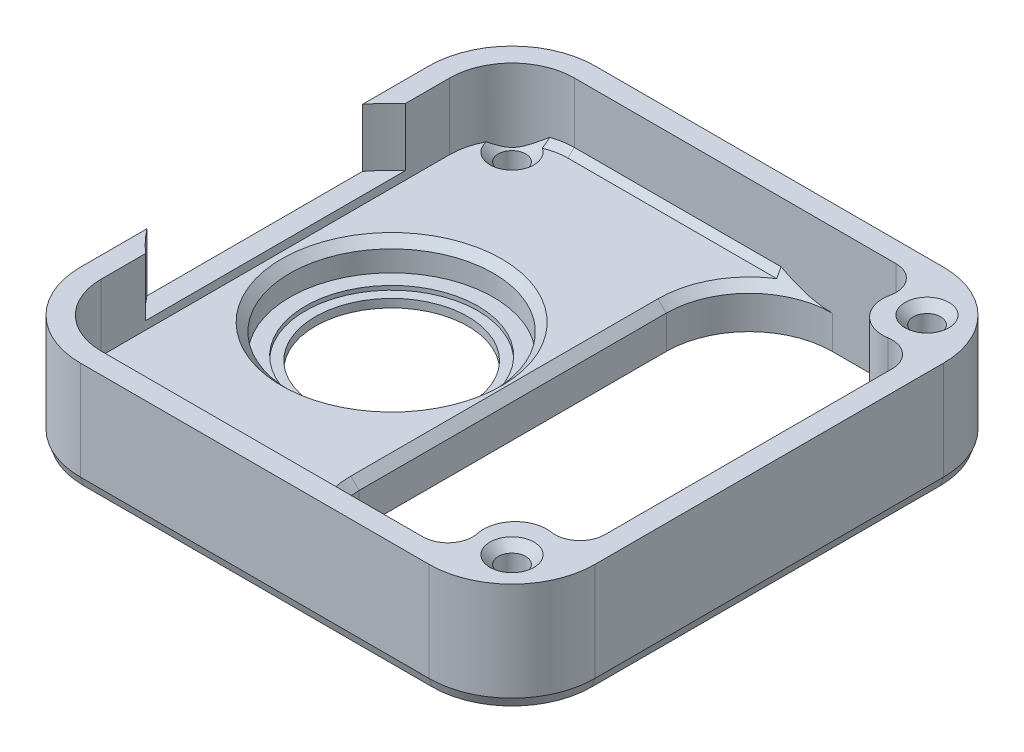
SolidWorks part; units mm, degrees
ref_plane "Alzado" through (0, 0, 0) normal (0, 0, 1) x (1, 0, 0)
ref_plane "Planta" through (0, 0, 0) normal (0, 1, 0) x (1, 0, 0)
ref_plane "Vista lateral" through (0, 0, 0) normal (1, 0, 0) x (0, 0, -1)
sketch "Croquis1" plane through (0, 0, 0) normal (0, 1, 0) x (1, 0, 0)
  line L0 (0, 31) -> (62, 31)
  line L1 (62, -31) -> (0, -31)
  line L2 (62, 31) -> (62, -31)
  line L3 (0, 31) -> (0, -31)
  point P4 (0, 0)
  dimension "D1" = 62
  dimension "D2" = 62
extrude "Saliente-Extruir1" add sketch "Croquis1" along normal blind 13
fillet "Redondeo1" radius 10 2 edges at (62, 6.5, -31) (62, 6.5, 31)
fillet "Redondeo2" radius 10 2 edges at (0, 6.5, 31) (0, 6.5, -31)
shell "Vaciado1" thickness 2.5 removed face at (31, 13, 0) removed face at (31, 0, 0)
sketch "Croquis2" plane through (0, 13, 0) normal (0, 1, 0) x (1, 0, 0)
  line L0 (0, 21) -> (0, -21) construction
  line L1 (59.5, -21) -> (59.5, 21) construction
  circle A0 centre (16.5, 0) radius 21
  point P7 (0, 0)
  dimension "D1" = 42
  dimension "D2" = 43
extrude "Cortar-Extruir1" cut sketch "Croquis2" against normal blind 7
sketch "Croquis4" plane through (0, 0, 0) normal (0, -1, 0) x (1, 0, 0)
  line L1 (7.0857, 29.1574) -> (31.0857, 29.1574)
  line L2 (2.0857, 24.1574) -> (2.0857, -24.9602)
  line L3 (7.0857, -29.9602) -> (31.0857, -29.9602)
  line L4 (31.0857, 29.1574) -> (31.0857, -29.9602)
  arc A0 (7.0857, 29.1574) -> (2.0857, 24.1574) centre (7.0857, 24.1574) ccw
  arc A1 (2.0857, -24.9602) -> (7.0857, -29.9602) centre (7.0857, -24.9602) ccw
  point P6 (2.0857, 29.1574)
  dimension "D2" = 5
  dimension "D1" = 29
extrude "Saliente-Extruir2" add sketch "Croquis4" against normal blind 5
sketch "Croquis6" plane through (0, 5, 0) normal (0, 1, 0) x (1, 0, 0)
  line L0 (59.5, -21) -> (59.5, 21) construction
  line L1 (0, 12.9904) -> (0, -12.9904) construction
  circle A0 centre (16.5, 0) radius 12.25
  point P7 (0, 0)
  dimension "D1" = 24.5
  dimension "D2" = 43
extrude "Cortar-Extruir4" cut sketch "Croquis6" against normal blind 4
sketch "Croquis7" plane through (0, 13, 0) normal (0, 1, 0) x (1, 0, 0)
  circle A0 centre (16.5, 0) radius 12.25
fillet "Redondeo3" radius 10 2 edges at (31.0857, 2.5, 28.5) (31.0857, 2.5, -28.5)
sketch "Croquis8" plane through (0, 13, 0) normal (0, 1, 0) x (1, 0, 0)
  line L0 (-6.7713, 0) -> (82.6429, 0) construction
  circle A0 centre (55.4301, 24.0427) radius 3.8135
  circle A1 centre (55.4301, -24.0427) radius 3.8135
extrude "Saliente-Extruir3" add sketch "Croquis8" against normal up to surface (13 mm away) up to face at (45.7884, 0, 0)
fillet "Redondeo4" radius 3 4 edges at (59.158, 6.5, 23.239) (55.0768, 6.5, 27.8398) (55.0768, 6.5, -27.8398) (59.158, 6.5, -23.239)
sketch "Croquis9" plane through (0, 13, 0) normal (0, 1, 0) x (1, 0, 0)
  line L0 (52, 31) -> (10, 31) construction
  line L1 (6, 25) -> (56, 25) construction
  line L2 (6, 25) -> (6, -25) construction
  line L3 (6, -25) -> (56, -25) construction
  line L4 (56, 25) -> (56, -25) construction
  line L5 (0, 21) -> (0, 12.9904) construction
  circle A0 centre (6, 25) radius 1.65
  circle A1 centre (56, -25) radius 1.65
  circle A2 centre (56, 25) radius 1.65
  circle A3 centre (6, -25) radius 1.65
  point P5 (6, 0)
  dimension "D1" = 3.3
  dimension "D2" = 50
  dimension "D3" = 6
  dimension "D4" = 6
extrude "Cortar-Extruir7" cut sketch "Croquis9" against normal through all and the other way through all
chamfer "Chaflán1" distance 1 angle 45 4 edges at (56, 13, 23.35) (56, 13, -26.65) (6, 5, 23.35) (6, 5, -26.65)
chamfer "Chaflán2" distance 1 angle 45 1 edges at (16.5, 5, 12.25)
chamfer "Chaflán3" distance 1 angle 45 3 edges at (34.0147, 5, -25.5711) (34.0147, 5, 25.5711) (31.0857, 5, 0)
chamfer "Chaflán4" distance 0.4 angle 70 8 edges at (31, 0, -31) (2.9289, 0, -28.0711) (59.0711, 0, -28.0711) (0, 0, 0) (62, 0, 0) (2.9289, 0, 28.0711) (59.0711, 0, 28.0711) (31, 0, 31) first distance on face at (6, 0, 26.65)
chamfer "Chaflán5" distance 1 angle 45 4 edges at (56, 0, -23.35) (56, 0, 26.65) (6, 0, 26.65) (6, 0, -23.35)
sketch "Croquis10" plane through (0, 1, 0) normal (0, 1, 0) x (1, 0, 0)
  circle A0 centre (16.5, 0) radius 14.0006
  circle A1 centre (16.5, 0) radius 10.397
extrude "Saliente-Extruir4" add sketch "Croquis10" along normal blind 0.5
sketch "Croquis11" plane through (0, 1, 0) normal (0, 1, 0) x (1, 0, 0)
  circle A0 centre (16.5, 0) radius 9.1929
extrude "Cortar-Extruir8" cut sketch "Croquis11" against normal through all
chamfer "Chaflán6" distance 0.75 angle 45 4 edges at (8.1734, 5, 28.2742) (23.2516, 5, 28.5) (8.1734, 5, -28.2742) (23.2516, 5, -28.5)
